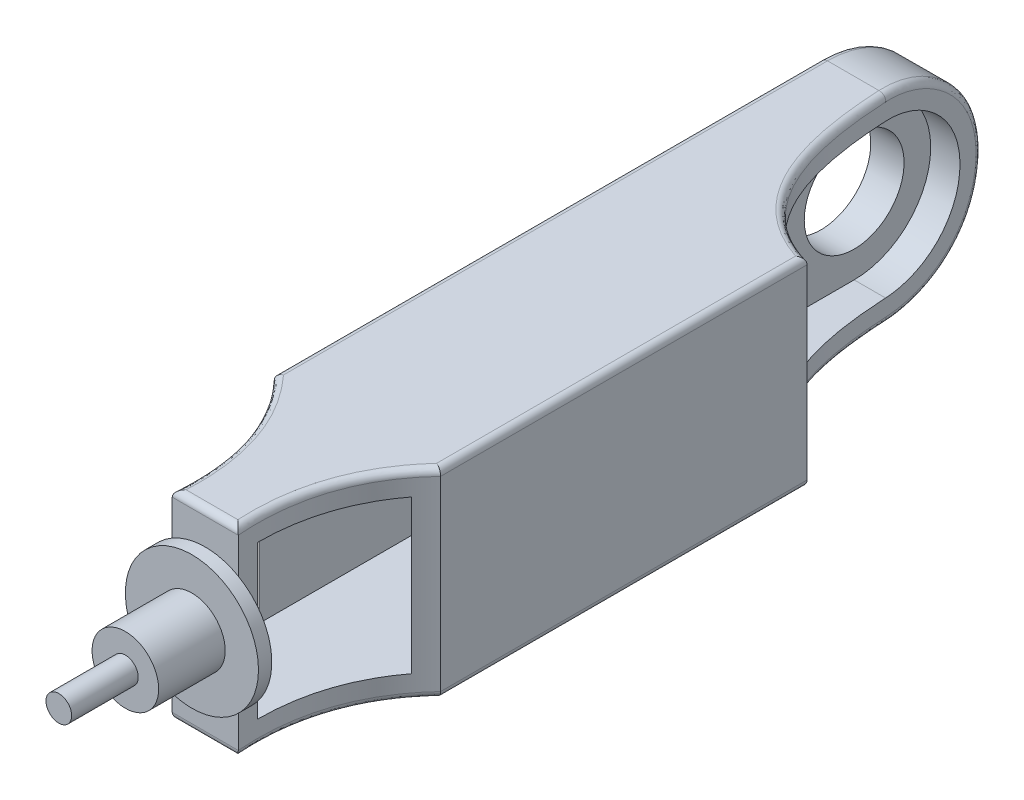
SolidWorks part; units mm, degrees
ref_plane "Front Plane" through (0, 0, 0) normal (0, 0, 1) x (1, 0, 0)
ref_plane "Top Plane" through (0, 0, 0) normal (0, 1, 0) x (1, 0, 0)
ref_plane "Right Plane" through (0, 0, 0) normal (1, 0, 0) x (0, 0, -1)
sketch "Sketch1" plane through (0, 0, 0) normal (0, 0, 1) x (1, 0, 0)
  line L1 (-12.5, -15) -> (12.5, -15)
  line L2 (-12.5, -15) -> (-12.5, 15)
  line L3 (-12.5, 15) -> (12.5, 15)
  line L4 (12.5, -15) -> (12.5, 15)
  line L5 (-12.5, -15) -> (12.5, 15) construction
  line L6 (-12.5, 15) -> (12.5, -15) construction
  point P0 (0, 0)
  dimension "D1" = 30
  dimension "D2" = 25
extrude "Boss-Extrude1" add sketch "Sketch1" along normal blind 120
sketch "Sketch2" plane through (12.5, 0, 0) normal (1, 0, 0) x (0, 0, -1)
  line L0 (0, 0) -> (-120, 0) construction
  line L1 (0, -15) -> (0, 15) construction
  line L2 (-120, -15) -> (-120, 15) construction
  line L3 (-15, -15) -> (0, -15)
  line L4 (0, -15) -> (0, 15)
  line L5 (0, 15) -> (-15, 15)
  circle A0 centre (-15, 0) radius 15
  line M2 (0, -15) -> (0, 15)
  line M3 (0, 15) -> (-120, 15)
  line M5 (-120, -15) -> (0, -15)
  dimension "D1" = 30
  dimension "D2" = 15
extrude "Cut-Extrude1" cut sketch "Sketch2" against normal up to next contours A0 M5 M2 | A0 L4 M3 region at (12.5, -11.6495, 3.3505) region at (12.5, 11.6495, 3.3505)
ref_plane "Plane1" through (0, -15, 0) normal (0, -1, 0) x (-1, 0, 0)
sketch "Sketch3" plane through (0, -15, 0) normal (0, -1, 0) x (1, 0, 0)
  line L0 (12.5, 120) -> (12.5, 15) construction
  line L1 (12.5, 42.0649) -> (12.5, 0)
  line L2 (12.5, 0) -> (-3.4546, 0)
  spline S0 degree 3 poles (-3.4546, 0) (-1.7635, 8.7145) (-6.7871, 36.4103) (12.5, 42.0649) knots 0 0 0 0 1 1 1 1
extrude "Cut-Extrude2" cut sketch "Sketch3" against normal up to next
sketch "Sketch4" plane through (12.5, 0, 0) normal (1, 0, 0) x (0, 0, -1)
  line L0 (0, 0) -> (-108.2697, 0) construction
  line L1 (-15, 11.5) -> (-42.0649, 11.5)
  line L2 (-42.0649, 15) -> (-42.0649, -15) construction
  line L3 (-42.0649, 11.5) -> (-42.0649, -11.5)
  line L4 (-42.0649, -11.5) -> (-15, -11.5)
  arc A0 (-15, -11.5) -> (-15, 11.5) centre (-15, 0) ccw
  dimension "D1" = 11.5
extrude "Cut-Extrude3" cut sketch "Sketch4" against normal blind 20
sketch "Sketch5" plane through (0, 0, 120) normal (0, 0, 1) x (1, 0, 0)
  line L0 (-12.5, -15) -> (12.5, -15) construction
  line L1 (10.5, 11.5) -> (-7.5, 11.5)
  line L2 (10.5, 11.5) -> (10.5, -11.5)
  line L3 (10.5, -11.5) -> (-7.5, -11.5)
  line L4 (-7.5, 11.5) -> (-7.5, -11.5)
  line L5 (12.5, -15) -> (12.5, 15) construction
  line L6 (12.5, 15) -> (-12.5, 15) construction
  dimension "D1" = 3.5
  dimension "D2" = 20
  dimension "D3" = 3.5
  dimension "D4" = 2
extrude "Cut-Extrude4" cut sketch "Sketch5" against normal up to next
sketch "Sketch8" plane through (-12.5, 0, 0) normal (-1, 0, 0) x (0, 0, 1)
  line L0 (0, 0) -> (15, 0) construction
  circle A0 centre (15, 0) radius 7.5
  dimension "D1" = 15
extrude "Cut-Extrude5" cut sketch "Sketch8" against normal up to next
sketch "Sketch10" plane through (0, 0, 120) normal (0, 0, 1) x (1, 0, 0)
  line L1 (12.5, -15) -> (-12.5, -15)
  line L2 (12.5, -15) -> (12.5, 15)
  line L3 (12.5, 15) -> (-12.5, 15)
  line L4 (-12.5, -15) -> (-12.5, 15)
extrude "Boss-Extrude2" add sketch "Sketch10" against normal blind 3
sketch "Sketch11" plane through (0, 0, 120) normal (0, 0, 1) x (1, 0, 0)
  circle A0 centre (0, 0) radius 10
  dimension "D1" = 20
extrude "Boss-Extrude3" add sketch "Sketch11" along normal blind 2
sketch "Sketch12" plane through (0, 0, 122) normal (0, 0, 1) x (1, 0, 0)
  circle A0 centre (0, 0) radius 5
  dimension "D1" = 10
extrude "Boss-Extrude4" add sketch "Sketch12" along normal blind 10
sketch "Sketch13" plane through (0, 0, 132) normal (0, 0, 1) x (1, 0, 0)
  circle A0 centre (0, 0) radius 1.93
extrude "Boss-Extrude5" add sketch "Sketch13" along normal blind 10
ref_plane "Plane2" through (0, -15, 0) normal (0, -1, 0) x (-1, 0, 0)
sketch "Sketch14" plane through (0, -15, 0) normal (0, -1, 0) x (-1, 0, 0)
  line L0 (0, 0) -> (0, -151.2963) construction
  line L1 (12.5, -120) -> (12.5, -15) construction
  line L2 (-10, -120) -> (10, -120) construction
  line L3 (12.5, -97.127) -> (12.5, -120)
  line L4 (12.5, -120) -> (4.9598, -120)
  line L5 (-12.5, -97.127) -> (-12.5, -120)
  line L6 (-12.5, -120) -> (-4.9598, -120)
  spline S0 degree 2 poles (12.5, -97.127) (3.8635, -106.3202) (4.9598, -120) knots 0 0 0 1 1 1
  spline S1 degree 2 poles (-12.5, -97.127) (-3.8635, -106.3202) (-4.9598, -120) knots 0 0 0 1 1 1
extrude "Cut-Extrude6" cut sketch "Sketch14" against normal up to next
fillet "Fillet3" radius 1 14 edges at (-3.4361, -1.7073, 0.0975) (-12.5, 0, 0) (12.5, 15, 69.5959) (0, 15, 120) (-12.5, 15, 56.0635) (12.5, -15, 69.5959) (-12.5, -15, 56.0635) (0, -15, 120)
sketch "Sketch15" plane through (0, 0, 142) normal (0, 0, 1) x (1, 0, 0)
  point P0 (0, 0)
sketch "Sketch16" plane through (-12.5, 0, 0) normal (-1, 0, 0) x (0, 0, 1)
  point P0 (15, 0)
